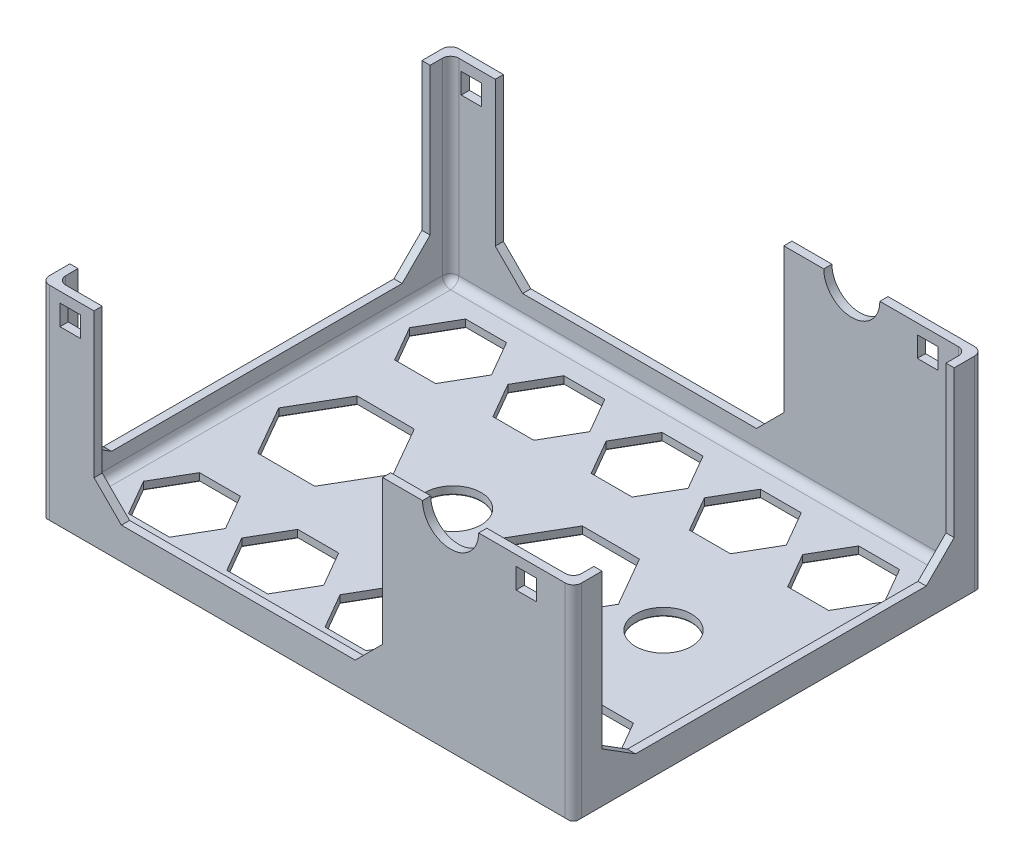
SolidWorks part; units mm, degrees
ref_plane "Front Plane" through (0, 0, 0) normal (0, 0, 1) x (1, 0, 0)
ref_plane "Top Plane" through (0, 0, 0) normal (0, 1, 0) x (1, 0, 0)
ref_plane "Right Plane" through (0, 0, 0) normal (1, 0, 0) x (0, 0, -1)
sketch "Sketch1" plane through (0, 0, 0) normal (0, 1, 0) x (1, 0, 0)
  line L1 (-65, -50) -> (65, -50)
  line L2 (-65, -50) -> (-65, 50)
  line L3 (-65, 50) -> (65, 50)
  line L4 (65, -50) -> (65, 50)
  line L5 (-65, -50) -> (65, 50) construction
  line L6 (-65, 50) -> (65, -50) construction
  point P0 (0, 0)
  dimension "D1" = 130
  dimension "D2" = 100
extrude "Boss-Extrude1" add sketch "Sketch1" along normal blind 50
shell "Shell1" thickness 2 removed face at (0, 50, 0)
chamfer "Chamfer1" distance 0.25 angle 45 4 edges at (65, 0, 0) (0, 0, -50) (0, 0, 50) (-65, 0, 0)
sketch "Sketch2" plane through (0, 0, 50) normal (0, 0, 1) x (1, 0, 0)
  line L0 (-65, 50) -> (65, 50) construction
  line L1 (65, 50) -> (65, 0.25) construction
  circle A0 centre (35, 50) radius 6.85
  dimension "D1" = 13.7
  dimension "D2" = 30
extrude "Cut-Extrude1" cut sketch "Sketch2" against normal through all
sketch "Sketch3" plane through (0, 2, 0) normal (0, 1, 0) x (1, 0, 0)
  line L0 (63, -48) -> (63, 48) construction
  circle A0 centre (-14.4, 0) radius 6.85
  circle A1 centre (37, 0) radius 6.85
  dimension "D1" = 13.7
  dimension "D2" = 51.4
  dimension "D3" = 26
extrude "Cut-Extrude2" cut sketch "Sketch3" against normal through all
sketch "Sketch4" plane through (0, 2, 0) normal (0, 1, 0) x (1, 0, 0)
  line L0 (-63, 48) -> (-63, -48) construction
  line L1 (-38, 33) -> (-43, 41.6603)
  line L2 (-43, 41.6603) -> (-53, 41.6603)
  line L3 (-53, 41.6603) -> (-58, 33)
  line L4 (-58, 33) -> (-53, 24.3397)
  line L5 (-53, 24.3397) -> (-43, 24.3397)
  line L6 (-43, 24.3397) -> (-38, 33)
  line L7 (28.15, 48) -> (-63, 48) construction
  circle A0 centre (-48, 33) radius 8.6603 construction
  dimension "D1" = 15
  dimension "D2" = 15
  dimension "D3" = 20
extrude "Cut-Extrude3" cut sketch "Sketch4" against normal through all
pattern_linear "LPattern1" count 5 spacing 24 along (1, 0, 0) count 2 spacing 65 along (0, 0, 1) of "Cut-Extrude3"
sketch "Sketch5" plane through (0, 2, 0) normal (0, 1, 0) x (1, 0, 0)
  line L1 (-35.9759, 12.1104) -> (-49.9759, 12.1382)
  line L2 (-49.9759, 12.1382) -> (-57, 0.0278)
  line L3 (-57, 0.0278) -> (-50.0241, -12.1104)
  line L4 (-50.0241, -12.1104) -> (-36.0241, -12.1382)
  line L5 (-36.0241, -12.1382) -> (-29, -0.0278)
  line L6 (-29, -0.0278) -> (-35.9759, 12.1104)
  line L7 (-63, 48) -> (-63, -48) construction
  circle A0 centre (-43, 0) radius 12.1244 construction
  dimension "D1" = 28
  dimension "D3" = 20
extrude "Cut-Extrude4" cut sketch "Sketch5" against normal blind 60
pattern_linear "LPattern2" count 2 spacing 55 along (1, 0, 0) of "Cut-Extrude4"
sketch "Sketch8" plane through (0, 0, -50) normal (0, 0, -1) x (-1, 0, 0)
  line L0 (-18.3845, 50) -> (-18.3845, 14.7016)
  line L1 (-28.15, 50) -> (65, 50) construction
  line L2 (-18.3845, 14.7016) -> (-11.6999, 8.0171)
  line L3 (-11.6999, 8.0171) -> (45.4059, 8.0171)
  line L4 (45.4059, 8.0171) -> (52.0905, 14.7016)
  line L5 (52.0905, 14.7016) -> (52.0905, 50)
  line L6 (52.0905, 50) -> (-18.3845, 50)
  dimension "D1" = 135
  dimension "D2" = 135
extrude "Cut-Extrude7" cut sketch "Sketch8" against normal through all
sketch "Sketch9" plane through (-65, 0, 0) normal (-1, 0, 0) x (0, 0, 1)
  line L0 (-43, 50) -> (-43, 14.0818)
  line L1 (-50, 50) -> (50, 50) construction
  line L2 (-43, 14.0818) -> (-36.1682, 7.25)
  line L3 (-36.1682, 7.25) -> (34.8143, 7.25)
  line L4 (34.8143, 7.25) -> (43, 12.3823)
  line L5 (43, 12.3823) -> (43, 50)
  line L6 (43, 50) -> (-43, 50)
  line L7 (-50, 0.25) -> (50, 0.25) construction
  line L8 (-50, 50) -> (-50, 0.25) construction
  line L9 (50, 50) -> (50, 0.25) construction
  dimension "D1" = 7
  dimension "D2" = 7
  dimension "D3" = 7
  dimension "D4" = 135
extrude "Cut-Extrude8" cut sketch "Sketch9" against normal through all
fillet "Fillet1" radius 2 12 edges at (0, 2, -48) (-63, 2, 0) (63, 2, 0) (0, 2, 48) (63, 26, 48) (63, 26, -48) (-63, 26, -48) (-63, 26, 48) (-65, 25.125, -50) (-65, 25.125, 50) (65, 25.125, -50) (65, 25.125, 50)
chamfer "Chamfer2" distance 0.25 angle 45 72 edges at (40.5, 0, 36.3301) (40.5, 0, 27.6699) (48, 0, 23.3397) (55.5, 0, 27.6699) (55.5, 0, 36.3301) (48, 0, 40.6603) (40.5, 0, -28.6699) (40.5, 0, -37.3301) (48, 0, -41.6603) (55.5, 0, -37.3301) (55.5, 0, -28.6699) (48, 0, -24.3397) (12.0241, 0, -12.1243) (22.512, 0, -6.0413) (1.5121, 0, -6.083) (1.488, 0, 6.0413) (22.4879, 0, 6.083) (11.9759, 0, 12.1243) (31.5, 0, 27.6699) (24, 0, 23.3397) (16.5, 0, 27.6699) (16.5, 0, 36.3301) (24, 0, 40.6603) (31.5, 0, 36.3301) (-7.5, 0, 27.6699) (0, 0, 23.3397) (7.5, 0, 27.6699) (7.5, 0, 36.3301) (-7.5, 0, 36.3301) (0, 0, 40.6603) (24, 0, -41.6603) (16.5, 0, -37.3301) (16.5, 0, -28.6699) (31.5, 0, -37.3301) (31.5, 0, -28.6699) (24, 0, -24.3397) (-7.5, 0, -28.6699) (-7.5, 0, -37.3301) (0, 0, -41.6603) (7.5, 0, -37.3301) (7.5, 0, -28.6699) (0, 0, -24.3397) (-31.5, 0, -28.6699) (-31.5, 0, -37.3301) (-24, 0, -41.6603) (-16.5, 0, -37.3301) (-16.5, 0, -28.6699) (-24, 0, -24.3397) (-55.5, 0, -28.6699) (-55.5, 0, -37.3301) (-48, 0, -41.6603) (-40.5, 0, -37.3301) (-40.5, 0, -28.6699) (-48, 0, -24.3397) (-32.488, 0, -6.0413) (-42.9759, 0, -12.1243) (-53.4879, 0, -6.083) (-53.512, 0, 6.0413) (-43.0241, 0, 12.1243) (-32.5121, 0, 6.083) (-31.5, 0, 36.3301) (-31.5, 0, 27.6699) (-24, 0, 23.3397) (-16.5, 0, 27.6699) (-16.5, 0, 36.3301) (-24, 0, 40.6603) (-55.5, 0, 36.3301) (-55.5, 0, 27.6699) (-48, 0, 23.3397) (-40.5, 0, 27.6699) (-40.5, 0, 36.3301) (-48, 0, 40.6603)
fillet "Fillet2" radius 0.25 2 edges at (37, 0, 6.85) (-14.4, 0, 6.85)
sketch "Sketch10" plane through (0, 0, -50) normal (0, 0, -1) x (-1, 0, 0)
  line L0 (-63, 50) -> (-41.85, 50) construction
  line L1 (-56, 47.5) -> (-51, 47.5)
  line L2 (-56, 47.5) -> (-56, 42.5)
  line L3 (-56, 42.5) -> (-51, 42.5)
  line L4 (-51, 47.5) -> (-51, 42.5)
  line L5 (-63, 50) -> (-63, 0.25) construction
  dimension "D1" = 2.5
  dimension "D2" = 7
  dimension "D3" = 5
  dimension "D4" = 5
extrude "Cut-Extrude9" cut sketch "Sketch10" against normal through all
sketch "Sketch11" plane through (0, 0, -50) normal (0, 0, -1) x (-1, 0, 0)
  line L0 (-51, 47.5) -> (-56, 47.5) construction
  line L1 (55.4, 47.5) -> (60.4, 47.5)
  line L2 (55.4, 47.5) -> (55.4, 42.5)
  line L3 (55.4, 42.5) -> (60.4, 42.5)
  line L4 (60.4, 47.5) -> (60.4, 42.5)
  line L5 (63, 0.25) -> (63, 50) construction
  point P6 (60.4, 45)
  dimension "D1" = 5
  dimension "D2" = 2.6
extrude "Cut-Extrude10" cut sketch "Sketch11" against normal through all
